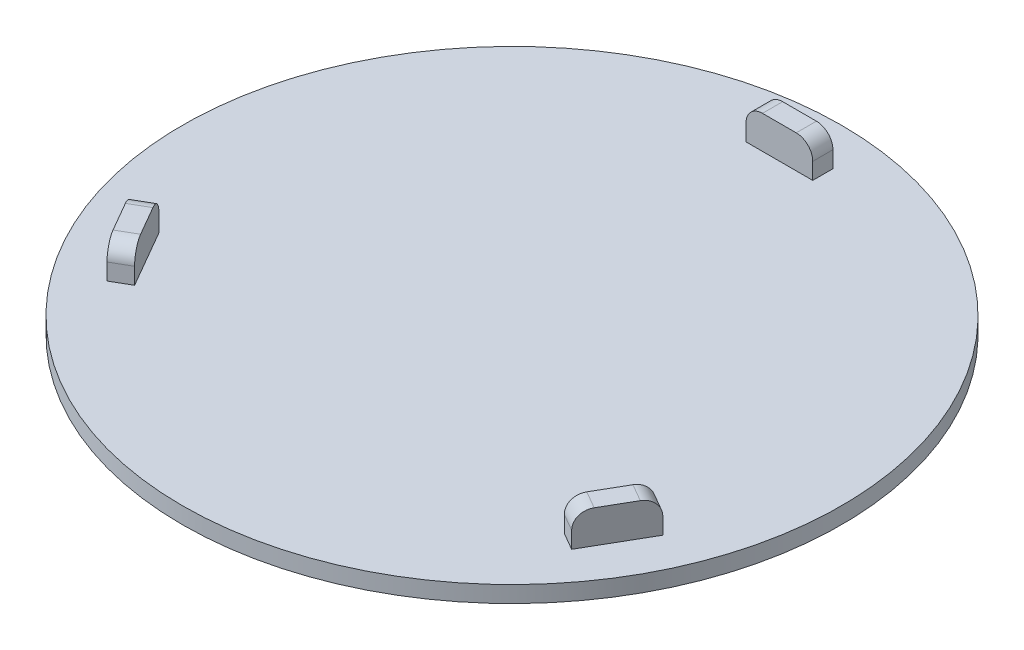
SolidWorks part; units mm, degrees
ref_plane "Front Plane" through (0, 0, 0) normal (0, 0, 1) x (1, 0, 0)
ref_plane "Top Plane" through (0, 0, 0) normal (0, 1, 0) x (1, 0, 0)
ref_plane "Right Plane" through (0, 0, 0) normal (1, 0, 0) x (0, 0, -1)
sketch "Sketch1" plane through (0, 0, 0) normal (0, 1, 0) x (1, 0, 0)
  circle A0 centre (0, 0) radius 40
  dimension "D1" = 80
extrude "Boss-Extrude1" add sketch "Sketch1" along normal blind 2
sketch "Sketch2" plane through (0, 2, 0) normal (0, 1, 0) x (1, 0, 0)
  line L0 (-4.2, 35.05) -> (4.2, 35.05)
  line L1 (-4.2, 35.05) -> (-4.2, 32.3)
  line L2 (4.2, 35.05) -> (4.2, 32.3)
  line L3 (-4.2, 32.3) -> (4.2, 32.3)
  line L4 (-4.2, 35.05) -> (4.2, 32.3) construction
  line L5 (4.2, 35.05) -> (-4.2, 32.3) construction
  line L6 (32.4542, -13.8877) -> (28.2542, -21.1623)
  line L7 (32.4542, -13.8877) -> (30.0726, -12.5127)
  line L8 (28.2542, -21.1623) -> (25.8726, -19.7873)
  line L9 (30.0726, -12.5127) -> (25.8726, -19.7873)
  line L10 (32.4542, -13.8877) -> (25.8726, -19.7873) construction
  line L11 (28.2542, -21.1623) -> (30.0726, -12.5127) construction
  line L12 (-28.2542, -21.1623) -> (-32.4542, -13.8877)
  line L13 (-28.2542, -21.1623) -> (-25.8726, -19.7873)
  line L14 (-32.4542, -13.8877) -> (-30.0726, -12.5127)
  line L15 (-25.8726, -19.7873) -> (-30.0726, -12.5127)
  line L16 (-28.2542, -21.1623) -> (-30.0726, -12.5127) construction
  line L17 (-32.4542, -13.8877) -> (-25.8726, -19.7873) construction
  point P1 (0, 33.675)
  point P9 (29.1634, -16.8375)
  point P14 (-29.1634, -16.8375)
  point P19 (0, 0)
  dimension "D1" = 2.75
  dimension "D2" = 8.4
  dimension "D3" = 32.3
  dimension "D4" = 3
extrude "Boss-Extrude2" add sketch "Sketch2" along normal blind 4
fillet "Fillet1" [suppressed] radius 2
sketch "Sketch3" plane through (0, 0, 0) normal (0, -1, 0) x (1, 0, 0)
  circle A1 centre (0, 0) radius 34
  circle A2 centre (0, 0) radius 36
  circle A3 centre (0, 0) radius 36
  dimension "D1" = 4
  dimension "D2" = 2
extrude "Boss-Extrude3" add sketch "Sketch3" along normal blind 2
fillet "Fillet2" radius 1 2 edges at (0, -2, -36) (0, -2, -34)
sketch "Sketch4" plane through (0, 0, 0) normal (0, -1, 0) x (1, 0, 0)
  line L0 (-1.5, -40) -> (-1.5, -1.5)
  line L1 (-1.5, -40) -> (1.5, -40)
  line L2 (-1.5, 40) -> (1.5, 40)
  line L3 (1.5, -40) -> (1.5, -1.5)
  line L4 (-1.5, -40) -> (1.5, 40) construction
  line L5 (-1.5, 40) -> (1.5, -40) construction
  line L6 (-40, 1.5) -> (-1.5, 1.5)
  line L7 (-40, 1.5) -> (-40, -1.5)
  line L8 (40, 1.5) -> (40, -1.5)
  line L9 (-40, -1.5) -> (-1.5, -1.5)
  line L10 (-40, 1.5) -> (40, -1.5) construction
  line L11 (40, 1.5) -> (-40, -1.5) construction
  line L12 (1.5, -1.5) -> (40, -1.5)
  line L13 (1.5, 1.5) -> (40, 1.5)
  line L14 (-0.0562, 1.5) -> (0.0562, 1.5)
  line L15 (-1.5, 1.5) -> (-1.5, 40)
  line L16 (-1.5, -0.0563) -> (-1.5, 0.0562)
  line L17 (-0.0563, -1.5) -> (0.0563, -1.5)
  line L18 (1.5, -0.0563) -> (1.5, 0.0562)
  line L19 (1.5, 1.5) -> (1.5, 40)
  point P1 (0, 0)
  point P2 (0, 0)
  dimension "D1" = 3
  dimension "D2" = 3
extrude "Cut-Extrude1" cut sketch "Sketch4" along normal up to next contours L3 L12 L8 L13 L19 L2 L15 L6 L7 L9 L0 L1
sketch "Sketch5" plane through (0, 6, 0) normal (0, 1, 0) x (1, 0, 0)
  line L4 (-28.1993, -20.9574) -> (-26.0775, -19.7324)
  line L5 (-26.0775, -19.7324) -> (-30.1275, -12.7176)
  line L6 (-30.1275, -12.7176) -> (-32.2493, -13.9426)
  line L7 (-32.2493, -13.9426) -> (-28.1993, -20.9574)
  line L8 (32.2493, -13.9426) -> (30.1275, -12.7176)
  line L9 (30.1275, -12.7176) -> (26.0775, -19.7324)
  line L10 (26.0775, -19.7324) -> (28.1993, -20.9574)
  line L11 (28.1993, -20.9574) -> (32.2493, -13.9426)
  line L12 (32.2493, -13.9426) -> (30.1275, -12.7176)
  line L13 (30.1275, -12.7176) -> (26.0775, -19.7324)
  line L14 (26.0775, -19.7324) -> (28.1993, -20.9574)
  line L15 (28.1993, -20.9574) -> (32.2493, -13.9426)
  line L16 (32.4542, -13.8877) -> (30.0726, -12.5127)
  line L17 (30.0726, -12.5127) -> (25.8726, -19.7873)
  line L18 (25.8726, -19.7873) -> (28.2542, -21.1623)
  line L19 (28.2542, -21.1623) -> (32.4542, -13.8877)
  line L20 (32.4542, -13.8877) -> (30.0726, -12.5127)
  line L21 (30.0726, -12.5127) -> (25.8726, -19.7873)
  line L22 (25.8726, -19.7873) -> (28.2542, -21.1623)
  line L23 (28.2542, -21.1623) -> (32.4542, -13.8877)
  line L24 (-28.2542, -21.1623) -> (-25.8726, -19.7873)
  line L25 (-25.8726, -19.7873) -> (-30.0726, -12.5127)
  line L26 (-30.0726, -12.5127) -> (-32.4542, -13.8877)
  line L27 (-32.4542, -13.8877) -> (-28.2542, -21.1623)
  line L28 (-4.05, 34.9) -> (-4.05, 32.45)
  line L29 (-4.05, 32.45) -> (4.05, 32.45)
  line L30 (4.05, 32.45) -> (4.05, 34.9)
  line L31 (4.05, 34.9) -> (-4.05, 34.9)
  line L32 (-4.2, 35.05) -> (-4.2, 32.3)
  line L33 (-4.2, 32.3) -> (4.2, 32.3)
  line L34 (4.2, 32.3) -> (4.2, 35.05)
  line L35 (4.2, 35.05) -> (-4.2, 35.05)
  point P26 (0, 0)
  dimension "D1" = 0.15
  dimension "D2" = 0
  dimension "D3" = 3
extrude "Cut-Extrude2" cut sketch "Sketch5" against normal up to surface (4 mm away) up to face at (0, 2, 40)
fillet "Fillet3" radius 2 6 edges at (-31.1884, 6, 13.3301) (-27.1384, 6, 20.3449) (27.1384, 6, 20.3449) (31.1884, 6, 13.3301) (4.05, 6, -33.675) (-4.05, 6, -33.675)
